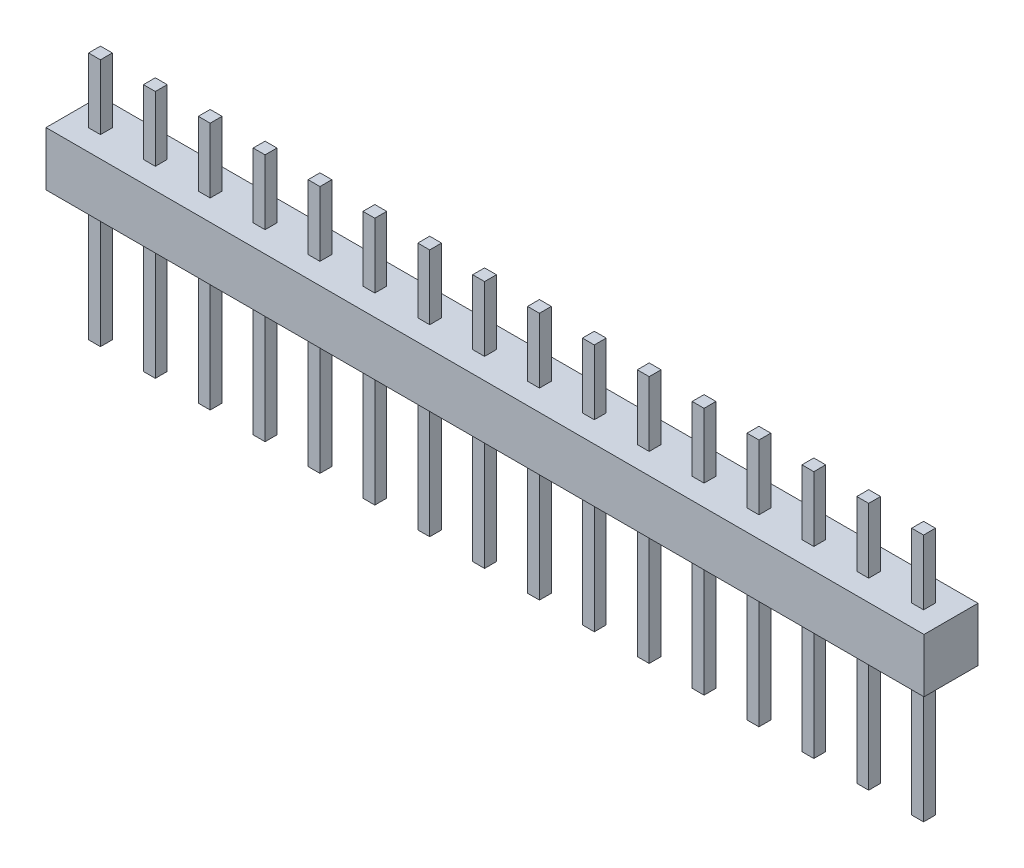
SolidWorks part; units mm, degrees
ref_plane "Front Plane" through (0, 0, 0) normal (0, 0, 1) x (1, 0, 0)
ref_plane "Top Plane" through (0, 0, 0) normal (0, 1, 0) x (1, 0, 0)
ref_plane "Right Plane" through (0, 0, 0) normal (1, 0, 0) x (0, 0, -1)
sketch "Sketch1" plane through (0, 0, 0) normal (0, 0, 1) x (1, 0, 0)
  line L1 (0, 0) -> (40.64, 0)
  line L2 (0, 0) -> (0, 2.5)
  line L3 (0, 2.5) -> (40.64, 2.5)
  line L4 (40.64, 0) -> (40.64, 2.5)
  dimension "D1" = 2.5
  dimension "D2" = 40.64
extrude "Boss-Extrude1" add sketch "Sketch1" along normal mid plane 2.5
sketch "Sketch2" plane through (0, 0, 0) normal (0, -1, 0) x (1, 0, 0)
  line L0 (0, 0) -> (40.64, 0) construction
  line L1 (40.64, 1.25) -> (40.64, -1.25) construction
  line L2 (3.535, -0.275) -> (4.085, -0.275)
  line L3 (0.995, -0.275) -> (1.545, -0.275)
  line L4 (0.995, -0.275) -> (0.995, 0.275)
  line L5 (0.995, 0.275) -> (1.545, 0.275)
  line L6 (1.545, -0.275) -> (1.545, 0.275)
  line L7 (0.995, -0.275) -> (1.545, 0.275) construction
  line L8 (0.995, 0.275) -> (1.545, -0.275) construction
  line L9 (3.535, -0.275) -> (3.535, 0.275)
  line L10 (3.535, 0.275) -> (4.085, 0.275)
  line L11 (4.085, -0.275) -> (4.085, 0.275)
  line L12 (3.535, -0.275) -> (4.085, 0.275) construction
  line L13 (3.535, 0.275) -> (4.085, -0.275) construction
  line L14 (1.27, 0) -> (3.81, 0) construction
  line L15 (6.075, -0.275) -> (6.625, -0.275)
  line L16 (6.075, -0.275) -> (6.075, 0.275)
  line L17 (6.075, 0.275) -> (6.625, 0.275)
  line L18 (6.625, -0.275) -> (6.625, 0.275)
  line L19 (6.075, -0.275) -> (6.625, 0.275) construction
  line L20 (6.075, 0.275) -> (6.625, -0.275) construction
  line L21 (8.615, -0.275) -> (9.165, -0.275)
  line L22 (8.615, -0.275) -> (8.615, 0.275)
  line L23 (8.615, 0.275) -> (9.165, 0.275)
  line L24 (9.165, -0.275) -> (9.165, 0.275)
  line L25 (8.615, -0.275) -> (9.165, 0.275) construction
  line L26 (8.615, 0.275) -> (9.165, -0.275) construction
  line L27 (11.155, -0.275) -> (11.705, -0.275)
  line L28 (11.155, -0.275) -> (11.155, 0.275)
  line L29 (11.155, 0.275) -> (11.705, 0.275)
  line L30 (11.705, -0.275) -> (11.705, 0.275)
  line L31 (11.155, -0.275) -> (11.705, 0.275) construction
  line L32 (11.155, 0.275) -> (11.705, -0.275) construction
  line L33 (13.695, -0.275) -> (14.245, -0.275)
  line L34 (13.695, -0.275) -> (13.695, 0.275)
  line L35 (13.695, 0.275) -> (14.245, 0.275)
  line L36 (14.245, -0.275) -> (14.245, 0.275)
  line L37 (13.695, -0.275) -> (14.245, 0.275) construction
  line L38 (13.695, 0.275) -> (14.245, -0.275) construction
  line L39 (16.235, -0.275) -> (16.785, -0.275)
  line L40 (16.235, -0.275) -> (16.235, 0.275)
  line L41 (16.235, 0.275) -> (16.785, 0.275)
  line L42 (16.785, -0.275) -> (16.785, 0.275)
  line L43 (16.235, -0.275) -> (16.785, 0.275) construction
  line L44 (16.235, 0.275) -> (16.785, -0.275) construction
  line L45 (18.775, -0.275) -> (19.325, -0.275)
  line L46 (18.775, -0.275) -> (18.775, 0.275)
  line L47 (18.775, 0.275) -> (19.325, 0.275)
  line L48 (19.325, -0.275) -> (19.325, 0.275)
  line L49 (18.775, -0.275) -> (19.325, 0.275) construction
  line L50 (18.775, 0.275) -> (19.325, -0.275) construction
  line L51 (21.315, -0.275) -> (21.865, -0.275)
  line L52 (21.315, -0.275) -> (21.315, 0.275)
  line L53 (21.315, 0.275) -> (21.865, 0.275)
  line L54 (21.865, -0.275) -> (21.865, 0.275)
  line L55 (21.315, -0.275) -> (21.865, 0.275) construction
  line L56 (21.315, 0.275) -> (21.865, -0.275) construction
  line L57 (23.855, -0.275) -> (24.405, -0.275)
  line L58 (23.855, -0.275) -> (23.855, 0.275)
  line L59 (23.855, 0.275) -> (24.405, 0.275)
  line L60 (24.405, -0.275) -> (24.405, 0.275)
  line L61 (23.855, -0.275) -> (24.405, 0.275) construction
  line L62 (23.855, 0.275) -> (24.405, -0.275) construction
  line L63 (26.395, -0.275) -> (26.945, -0.275)
  line L64 (26.395, -0.275) -> (26.395, 0.275)
  line L65 (26.395, 0.275) -> (26.945, 0.275)
  line L66 (26.945, -0.275) -> (26.945, 0.275)
  line L67 (26.395, -0.275) -> (26.945, 0.275) construction
  line L68 (26.395, 0.275) -> (26.945, -0.275) construction
  line L69 (28.935, -0.275) -> (29.485, -0.275)
  line L70 (28.935, -0.275) -> (28.935, 0.275)
  line L71 (28.935, 0.275) -> (29.485, 0.275)
  line L72 (29.485, -0.275) -> (29.485, 0.275)
  line L73 (28.935, -0.275) -> (29.485, 0.275) construction
  line L74 (28.935, 0.275) -> (29.485, -0.275) construction
  line L75 (31.475, -0.275) -> (32.025, -0.275)
  line L76 (31.475, -0.275) -> (31.475, 0.275)
  line L77 (31.475, 0.275) -> (32.025, 0.275)
  line L78 (32.025, -0.275) -> (32.025, 0.275)
  line L79 (31.475, -0.275) -> (32.025, 0.275) construction
  line L80 (31.475, 0.275) -> (32.025, -0.275) construction
  line L81 (34.015, -0.275) -> (34.565, -0.275)
  line L82 (34.015, -0.275) -> (34.015, 0.275)
  line L83 (34.015, 0.275) -> (34.565, 0.275)
  line L84 (34.565, -0.275) -> (34.565, 0.275)
  line L85 (34.015, -0.275) -> (34.565, 0.275) construction
  line L86 (34.015, 0.275) -> (34.565, -0.275) construction
  line L87 (36.555, -0.275) -> (37.105, -0.275)
  line L88 (36.555, -0.275) -> (36.555, 0.275)
  line L89 (36.555, 0.275) -> (37.105, 0.275)
  line L90 (37.105, -0.275) -> (37.105, 0.275)
  line L91 (36.555, -0.275) -> (37.105, 0.275) construction
  line L92 (36.555, 0.275) -> (37.105, -0.275) construction
  line L93 (39.095, -0.275) -> (39.645, -0.275)
  line L94 (39.095, -0.275) -> (39.095, 0.275)
  line L95 (39.095, 0.275) -> (39.645, 0.275)
  line L96 (39.645, -0.275) -> (39.645, 0.275)
  line L97 (39.095, -0.275) -> (39.645, 0.275) construction
  line L98 (39.095, 0.275) -> (39.645, -0.275) construction
  point P5 (1.27, 0)
  point P12 (3.81, 0)
  point P18 (6.35, 0)
  point P23 (8.89, 0)
  point P28 (11.43, 0)
  point P33 (13.97, 0)
  point P38 (16.51, 0)
  point P43 (19.05, 0)
  point P48 (21.59, 0)
  point P53 (24.13, 0)
  point P58 (26.67, 0)
  point P63 (29.21, 0)
  point P68 (31.75, 0)
  point P73 (34.29, 0)
  point P78 (36.83, 0)
  point P84 (39.37, 0)
  dimension "D1" = 0.55
  dimension "D3" = 1.27
  dimension "D4" = 2.54
  dimension "D2" = 16
extrude "Boss-Extrude2" add sketch "Sketch2" along normal blind 6 separate body
ref_axis "Axis1" through (1.27, 0, 0) along (0, -1, 0)
ref_axis "Axis2" through (39.37, 0, 0) along (0, -1, 0)
extrude "Boss-Extrude3" add sketch "Sketch2<2>" against normal blind 5.5 separate body
sketch "Sketch2<2>" plane through (0, 0, 0) normal (0, -1, 0) x (1, 0, 0) same geometry as "Sketch2"
